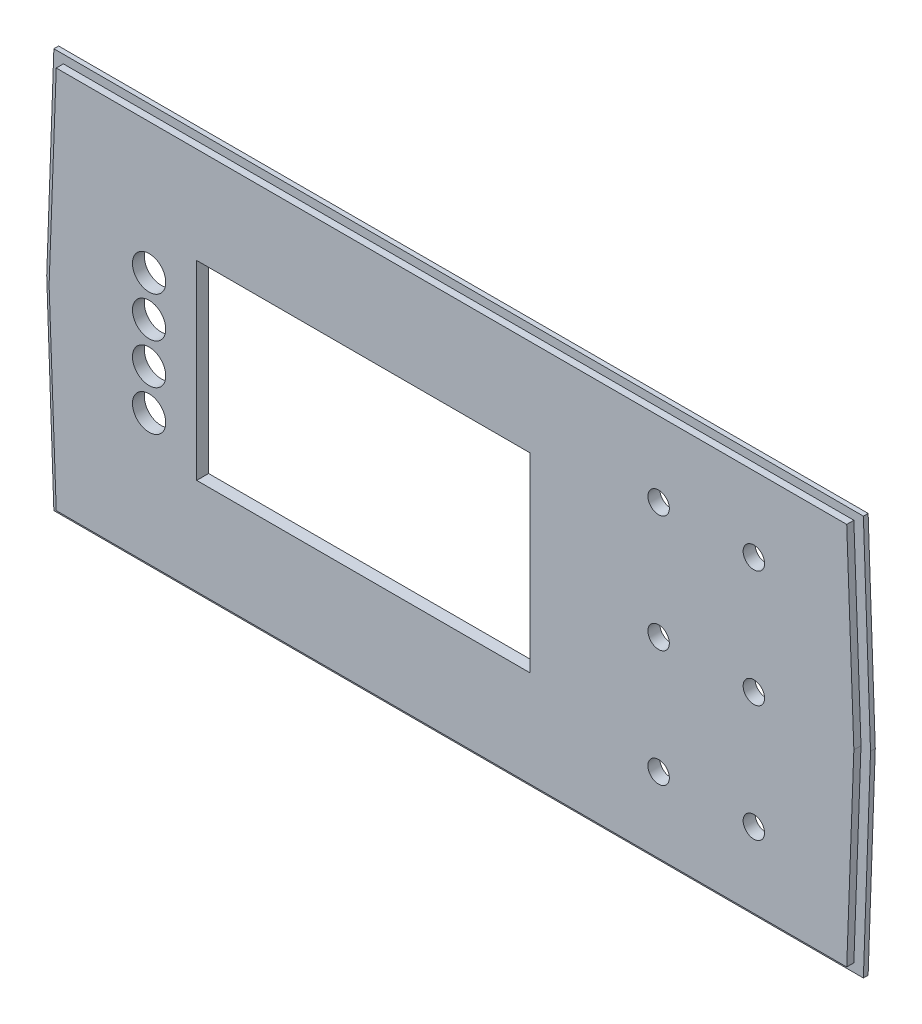
SolidWorks part; units mm, degrees
ref_plane "Front Plane" through (0, 0, 0) normal (0, 0, 1) x (1, 0, 0)
ref_plane "Top Plane" through (0, 0, 0) normal (0, 1, 0) x (1, 0, 0)
ref_plane "Right Plane" through (0, 0, 0) normal (1, 0, 0) x (0, 0, -1)
sketch "Sketch1" plane through (0, 0, 0) normal (0, 0, 1) x (1, 0, 0)
  line L1 (-85, 42) -> (85, 42)
  line L3 (-85, -42) -> (85, -42)
  line L5 (-85, 42) -> (85, -42) construction
  line L6 (-85, -42) -> (85, 42) construction
  line L7 (-86.5, 0) -> (-85, -42)
  line L8 (-85, 42) -> (-86.5, 0)
  line L9 (85, -42) -> (86.5, 0)
  line L10 (85, 42) -> (86.5, 0)
  point P0 (0, 0)
  dimension "D1" = 170
  dimension "D2" = 84
  dimension "D3" = 173
extrude "Boss-Extrude1" add sketch "Sketch1" along normal blind 1
sketch "Sketch2" plane through (0, 0, 1) normal (0, 0, 1) x (1, 0, 0)
  line L0 (-84.5, 0) -> (84.5, 0) construction
  line L1 (-83, 40.25) -> (83, 40.25)
  line L3 (-83, -40.25) -> (83, -40.25)
  line L5 (-83, 40.25) -> (83, -40.25) construction
  line L6 (-83, -40.25) -> (83, 40.25) construction
  line L7 (-83, -40.25) -> (-84.5, 0)
  line L8 (-84.5, 0) -> (-83, 40.25)
  line L9 (83, -40.25) -> (84.5, 0)
  line L10 (84.5, 0) -> (83, 40.25)
  point P0 (0, 0)
  dimension "D1" = 166
  dimension "D2" = 80.5
  dimension "D3" = 169
extrude "Boss-Extrude2" add sketch "Sketch2" along normal blind 1.5
sketch "Sketch3" plane through (0, 0, 0) normal (0, 0, -1) x (-1, 0, 0)
  line L0 (-85, 42) -> (85, 42) construction
  line L1 (-16.5, 20) -> (53.5, 20)
  line L2 (-16.5, 20) -> (-16.5, -20)
  line L3 (-16.5, -20) -> (53.5, -20)
  line L4 (53.5, 20) -> (53.5, -20)
  line L5 (-16.5, 20) -> (53.5, -20) construction
  line L6 (-16.5, -20) -> (53.5, 20) construction
  line L11 (-21, 28.5) -> (58, -28.5) construction
  line L12 (-21, -28.5) -> (58, 28.5) construction
  point P0 (18.5, 0)
  point P5 (18.5, 0)
  dimension "D1" = 40
  dimension "D2" = 70
  dimension "D3" = 68
  dimension "D5" = 42
extrude "Cut-Extrude1" cut sketch "Sketch3" against normal blind 10
sketch "Sketch4" plane through (0, 0, 0) normal (0, 0, -1) x (-1, 0, 0)
  line L1 (-70.5, 32) -> (-36.5, 32) construction
  line L2 (-70.5, 32) -> (-70.5, 17) construction
  line L3 (-70.5, 17) -> (-36.5, 17) construction
  line L4 (-36.5, 32) -> (-36.5, 17) construction
  line L6 (-36.5, -17) -> (-70.5, -17) construction
  line L7 (-70.5, 32) -> (-36.5, 17) construction
  line L8 (-70.5, 17) -> (-36.5, 32) construction
  line L9 (85, -42) -> (-85, -42) construction
  line L10 (-70.5, 7.5) -> (-36.5, 7.5) construction
  line L11 (-70.5, 7.5) -> (-70.5, -7.5) construction
  line L12 (-70.5, -7.5) -> (-36.5, -7.5) construction
  line L13 (-36.5, 7.5) -> (-36.5, -7.5) construction
  line L14 (-70.5, 7.5) -> (-36.5, -7.5) construction
  line L15 (-70.5, -7.5) -> (-36.5, 7.5) construction
  line L16 (-85, 42) -> (85, 42) construction
  line L17 (-36.5, -17) -> (-36.5, -32) construction
  line L18 (-36.5, -32) -> (-70.5, -32) construction
  line L19 (-70.5, -17) -> (-70.5, -32) construction
  line L20 (-36.5, -17) -> (-70.5, -32) construction
  line L21 (-36.5, -32) -> (-70.5, -17) construction
  circle A0 centre (-63.5, -24.5) radius 2.25
  circle A1 centre (-43.5, -24.5) radius 2.25
  circle A2 centre (-63.5, 0) radius 2.25
  circle A3 centre (-43.5, 0) radius 2.25
  circle A4 centre (-43.5, 24.5) radius 2.25
  circle A5 centre (-63.5, 24.5) radius 2.25
  point P1 (-53.5, 0)
  point P2 (-53.5, 24.5)
  point P7 (-53.5, -24.5)
  point P32 (-53.5, -24.5)
  point P33 (-53.5, -24.5)
  dimension "D3" = 4.5
  dimension "D4" = 4.5
  dimension "D5" = 4.5
  dimension "D6" = 4.5
  dimension "D7" = 10
  dimension "D8" = 10
  dimension "D11" = 10
  dimension "D16" = 4.5
  dimension "D17" = 4.5
  dimension "D20" = 15
  dimension "D1" = 34
  dimension "D2" = 33
  dimension "D9" = 24.5
  dimension "D10" = 10
  dimension "D12" = 15
  dimension "D13" = 24.5
  dimension "D14" = 10
  dimension "D15" = 10
  dimension "D18" = 10
  dimension "D19" = 10
  dimension "D21" = 15
  dimension "D22" = 34
  dimension "D23" = 34
  dimension "D24" = 17.5
  dimension "D25" = 42
  dimension "D26" = 66.5
extrude "Cut-Extrude3" cut sketch "Sketch4" against normal blind 10 contours A0 | A1 | A2 | A3 | A4 | A5 region at (63.5, -24.5, 0)
sketch "Sketch5" plane through (0, 0, 0) normal (0, 0, -1) x (-1, 0, 0)
  line L0 (-16.5, -20) -> (53.5, -20) construction
  line L1 (53.5, -20) -> (53.5, 20) construction
  line L2 (47.3111, 23) -> (71.3111, 23) construction
  line L3 (71.3111, 23) -> (71.3111, -23) construction
  line L4 (71.3111, -23) -> (47.3111, -23) construction
  line L5 (47.3111, -23) -> (47.3111, 23) construction
  line L6 (-85, 42) -> (85, 42) construction
  circle A0 centre (63.5, -4.25) radius 3.5
  circle A1 centre (63.5, 4.25) radius 3.5
  circle A2 centre (63.5, -12.75) radius 3.5
  circle A3 centre (63.5, 12.75) radius 3.5
  point P14 (47.3111, 0)
  point P17 (53.5, 0)
  dimension "D2" = 10
  dimension "D1" = 7
  dimension "D6" = 7.25
  dimension "D5" = 8.5
  dimension "D3" = 8.5
  dimension "D4" = 8.5
  dimension "D7" = 24
  dimension "D8" = 46
  dimension "D9" = 148.5
  dimension "D10" = 29.25
  dimension "D11" = 37.75
  dimension "D12" = 46.25
  dimension "D13" = 54.75
extrude "Cut-Extrude4" cut sketch "Sketch5" against normal up to surface (2.5 mm away) up to face at (61.25, 24.5, 2.5)
